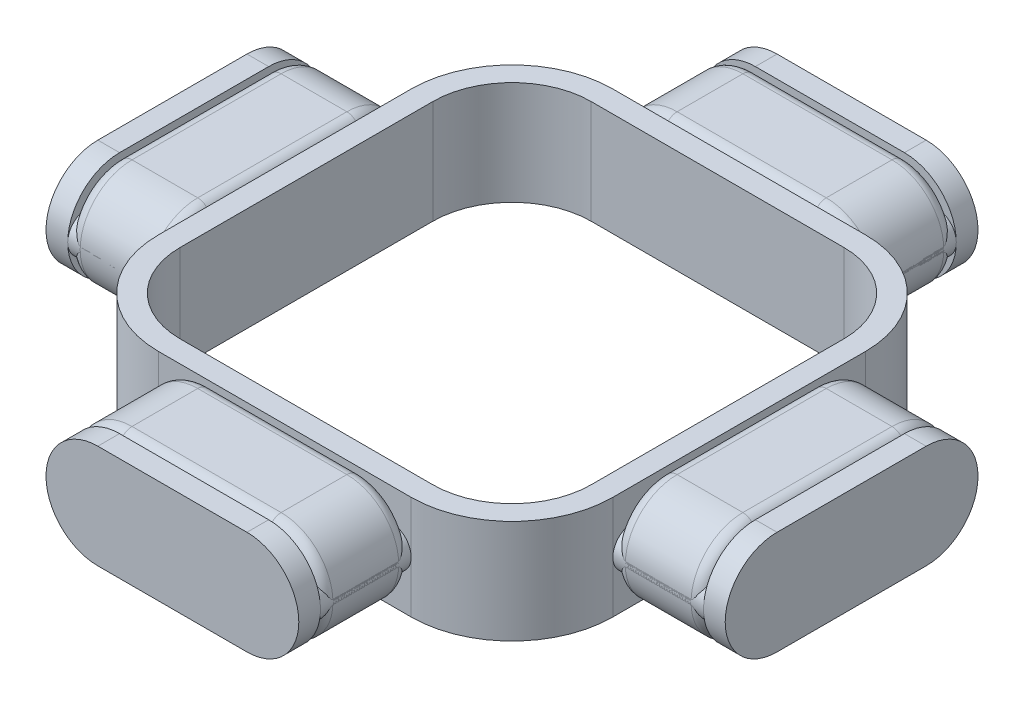
SolidWorks part; units mm, degrees
ref_plane "Front Plane" through (0, 0, 0) normal (0, 0, 1) x (1, 0, 0)
ref_plane "Top Plane" through (0, 0, 0) normal (0, 1, 0) x (1, 0, 0)
ref_plane "Right Plane" through (0, 0, 0) normal (1, 0, 0) x (0, 0, -1)
sketch "Sketch1" plane through (0, 0, 0) normal (0, 1, 0) x (1, 0, 0)
  line L0 (-33, 33) -> (33, 33)
  line L1 (39, 39) -> (-39, 39) construction
  line L2 (39, 39) -> (39, -39) construction
  line L3 (39, -39) -> (-39, -39) construction
  line L4 (-39, 39) -> (-39, -39) construction
  line L5 (39, 39) -> (-39, -39) construction
  line L6 (39, -39) -> (-39, 39) construction
  line L7 (-45, -45) -> (45, -45)
  line L8 (-45, -45) -> (-45, 45)
  line L9 (-45, 45) -> (45, 45)
  line L10 (45, -45) -> (45, 45)
  line L11 (-45, -45) -> (45, 45) construction
  line L12 (-45, 45) -> (45, -45) construction
  line L13 (33, -33) -> (33, 33)
  line L14 (-33, -33) -> (33, -33)
  line L15 (-33, -33) -> (-33, 33)
  circle A0 centre (39, 39) radius 2.75
  circle A1 centre (39, -39) radius 2.75
  circle A2 centre (-39, -39) radius 2.75
  circle A3 centre (-39, 39) radius 2.75
  point P0 (0, 0)
  point P6 (0, 0)
  dimension "D3" = 5.5
  dimension "D1" = 78
  dimension "D2" = 90
  dimension "D4" = 12
ref_axis "Axis1" through (0, 57.2807, 0) along (0, -1, 0)
sketch "Sketch4" plane through (0, 0, 0) normal (1, 0, 0) x (0, 0, -1)
  line L15 (-51.0432, 0) -> (-54.5291, 0)
  line L16 (-33, -8.3236) -> (-54.5291, -8.3236) construction
  line L17 (-33, -16.6473) -> (-33, 0)
  line L18 (-33, 0) -> (-36.4859, 0)
  line L19 (-54.5291, -16.6473) -> (-54.5291, 0)
  line L21 (-51.0432, 0) -> (-51.0432, -5.0977)
  line L22 (-51.0432, -5.0977) -> (-36.4859, -5.0977)
  line L23 (-36.4859, 0) -> (-36.4859, -5.0977)
  line L24 (-51.0432, 0) -> (-36.4859, 0) construction
  line L25 (-51.0432, -16.6473) -> (-54.5291, -16.6473)
  line L26 (-51.0432, -16.6473) -> (-51.0432, -11.5496)
  line L27 (-51.0432, -11.5496) -> (-36.4859, -11.5496)
  line L28 (-36.4859, -16.6473) -> (-36.4859, -11.5496)
  line L29 (-33, -16.6473) -> (-36.4859, -16.6473)
  line L30 (-45, 0) -> (45, 0) construction
extrude "Boss-Extrude3" add sketch "Sketch4" along normal mid plane 40.59
fillet "Fillet1" 2 edges at (20.295, -5.0977, 43.7646) (20.295, -11.5496, 43.7646) type full round first side face at (0, -5.0977, 43.7646) second side face at (0, -11.5496, 43.7646) middle face at (20.295, -8.3236, 43.7646)
fillet "Fillet2" 2 edges at (-20.295, -5.0977, 43.7646) (-20.295, -11.5496, 43.7646) type full round first side face at (-1.613, -5.0977, 43.7646) second side face at (-1.613, -11.5496, 43.7646) middle face at (-20.295, -8.3236, 43.7646)
fillet "Fillet5" 2 edges at (20.295, 0, 52.7862) (20.295, -16.6473, 52.7862) type full round first side face at (0, 0, 52.7862) second side face at (0, -16.6473, 52.7862) middle face at (20.295, -8.3236, 52.4376)
fillet "Fillet6" 2 edges at (-20.295, 0, 52.7862) (-20.295, -16.6473, 52.7862) type full round first side face at (-4.1618, 0, 52.7862) second side face at (-4.1618, -16.6473, 52.7862) middle face at (-20.295, -8.3236, 52.4376)
pattern_circular "CirPattern3" count 4 over 360 about axis through (0, 57.2807, 0) along (0, -1, 0) of bodies 119
sketch "Sketch7" plane through (0, 0, 0) normal (0, 1, 0) x (1, 0, 0)
  line L0 (33, -20.295) -> (20.295, -20.295) construction
  line L1 (20.295, -20.295) -> (20.295, -33) construction
  line L12 (-20.295, 36.4859) -> (20.295, 36.4859) construction
  line L13 (-20.295, 33) -> (20.295, 33) construction
  line L14 (-36.4859, -20.295) -> (-36.4859, 20.295) construction
  line L15 (-33, -20.295) -> (-33, 20.295) construction
  line L16 (20.295, -36.4859) -> (-20.295, -36.4859) construction
  line L17 (20.295, -33) -> (-20.295, -33) construction
  line L18 (33, 20.295) -> (33, -20.295) construction
  line L19 (36.4859, 20.295) -> (36.4859, -20.295) construction
  line L20 (-20.295, 36.4859) -> (20.295, 36.4859)
  line L21 (-20.295, 33) -> (20.295, 33)
  line L22 (-36.4859, -20.295) -> (-36.4859, 20.295)
  line L23 (-33, -20.295) -> (-33, 20.295)
  line L24 (20.295, -36.4859) -> (-20.295, -36.4859)
  line L25 (20.295, -33) -> (-20.295, -33)
  line L26 (33, 20.295) -> (33, -20.295)
  line L27 (36.4859, 20.295) -> (36.4859, -20.295)
  arc A0 (20.295, -33) -> (33, -20.295) centre (20.295, -20.295) ccw
  arc A1 (20.295, -36.4859) -> (36.4859, -20.295) centre (20.295, -20.295) ccw
  arc A2 (-33, -20.295) -> (-20.295, -33) centre (-20.295, -20.295) ccw
  arc A3 (-36.4859, -20.295) -> (-20.295, -36.4859) centre (-20.295, -20.295) ccw
  arc A4 (-20.295, 33) -> (-33, 20.295) centre (-20.295, 20.295) ccw
  arc A5 (-20.295, 36.4859) -> (-36.4859, 20.295) centre (-20.295, 20.295) ccw
  arc A6 (33, 20.295) -> (20.295, 33) centre (20.295, 20.295) ccw
  arc A7 (36.4859, 20.295) -> (20.295, 36.4859) centre (20.295, 20.295) ccw
  dimension "D1" = 4
extrude "Boss-Extrude4" add sketch "Sketch7" against normal up to surface (16.6473 mm away) up to face at (34.7429, -16.6473, 0)
sketch "Sketch9" plane through (0, 0, 36.4859) normal (0, 0, 1) x (1, 0, 0)
  line L0 (-30.8675, -8.3236) -> (30.8675, -8.3236) construction
  line L1 (-11.9714, -8.3236) -> (11.9714, -8.3236) construction
  line L2 (-11.9714, 0) -> (11.9714, 0)
  line L3 (-11.9714, -16.6473) -> (11.9714, -16.6473)
  arc A0 (-11.9714, 0) -> (-11.9714, -16.6473) centre (-11.9714, -8.3236) ccw
  arc A1 (11.9714, -16.6473) -> (11.9714, 0) centre (11.9714, -8.3236) ccw
  arc A2 (11.9714, -16.6473) -> (11.9714, 0) centre (11.9714, -8.3236) ccw construction
  point P6 (0, -8.3236)
extrude "Boss-Extrude5" add sketch "Sketch9" along normal up to surface (14.5573 mm away) separate body up to face at (0, -3.6764, 51.0432)
fillet "Fillet3" radius 2 8 edges at (0, -16.6473, 51.0432) (-20.295, -8.3236, 51.0432) (0, 0, 51.0432) (0, -16.6473, 36.4859) (-20.295, -8.3236, 36.4859) (0, 0, 36.4859) (20.295, -8.3236, 51.0432) (20.295, -8.3236, 36.4859)
pattern_circular "CirPattern5" count 4 over 360 about axis through (0, 57.2807, 0) along (0, -1, 0) of bodies 127
